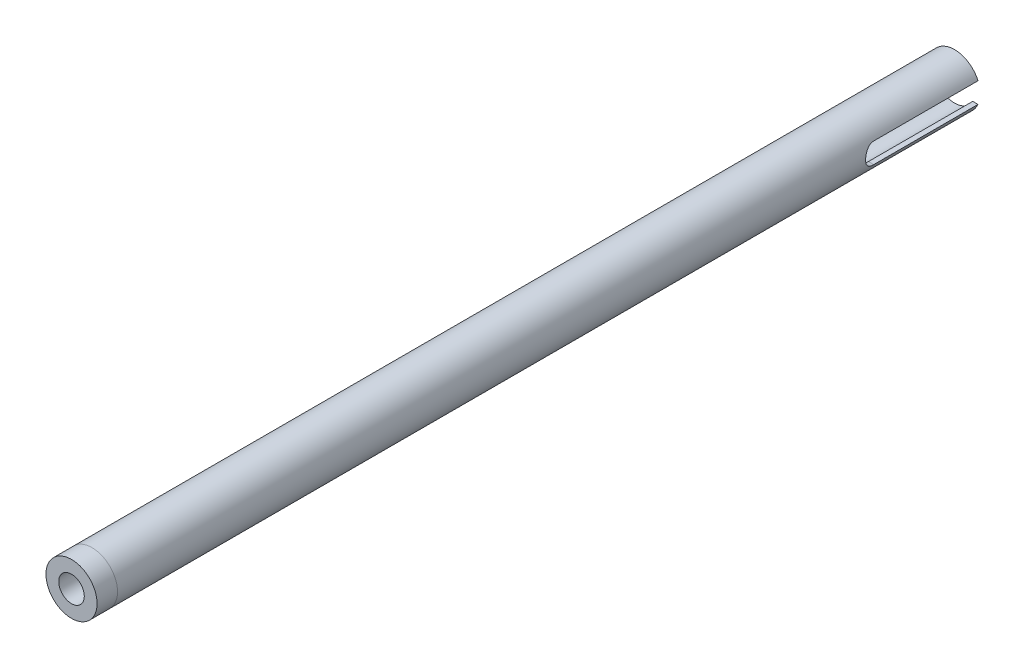
SolidWorks part; units mm, degrees
material "AISI 4130 Steel, annealed at 865C"
ref_plane "Front Plane" through (0, 0, 0) normal (0, 0, 1) x (1, 0, 0)
ref_plane "Top Plane" through (0, 0, 0) normal (0, 1, 0) x (1, 0, 0)
ref_plane "Right Plane" through (0, 0, 0) normal (1, 0, 0) x (0, 0, -1)
sketch "Axis" plane through (0, 0, 0) normal (0, 1, 0) x (1, 0, 0)
  line L0 (0, 0) -> (0, 274.208) construction
  line L1 (0, 0) -> (0, -28.575) construction
  line L2 (0, 274.208) -> (-7.9375, 274.208) construction
  line L4 (0, 295.0656) -> (-10.3187, 267.9508) construction
  dimension "D1" = 28.575
  dimension "D2" = 7.9375
sketch "Sketch1" plane through (0, 0, 0) normal (0, 0, 1) x (1, 0, 0)
  line L0 (-7.9375, 0) -> (7.9375, 0) construction
  line L1 (-7.2748, 3.175) -> (7.2748, 3.175)
  line L2 (-7.2748, -3.175) -> (7.2748, -3.175)
  circle A0 centre (0, 0) radius 7.9375
  circle A1 centre (0, 0) radius 6.4643
  circle A2 centre (0, 0) radius 3.9688
  dimension "D1" = 15.875
  dimension "D3" = 7.9375
  dimension "D2" = 1.4732
  dimension "D4" = 6.35
extrude "Threaded insert 1-1" add sketch "Sketch1" against normal blind 6.35 contours A2 L1 A1 | A1 L1 A0 | A2 L0 A1 L1 | A1 L0 A0 L1 | L0 A1 L2 A0 | L0 A2 L2 A1 | A2 L2 A1 | A1 L2 A0 | L0 A1 L2 A2 | L0 A0 L2 A1 | A0 L0 A1 L1 | A1 L0 A2 L1 region at (4.8156, 1.6537, 0) region at (4.8156, -1.6537, 0) region at (6.9501, 1.6161, 0) region at (6.9501, -1.6161, 0) region at (-4.8156, -1.6537, 0) region at (-4.8156, 1.6537, 0) region at (0, 4.6361, 0) region at (0, -4.6361, 0) region at (0, 6.6174, 0) region at (6.4528, -3.3281, 0) region at (-6.9501, -1.6161, 0) region at (-6.9501, 1.6161, 0)
extrude "Threaded insert 1-2" add sketch "Sketch1<3>" against normal blind 9.525 from surface contours A2 L1 A1 | A2 L0 A1 L1 | L0 A2 L2 A1 | A2 L2 A1 | L0 A1 L2 A2 | A1 L0 A2 L1 region at (4.8156, 1.6537, 0) region at (4.8156, -1.6537, 0) region at (-4.8156, -1.6537, 0) region at (-4.8156, 1.6537, 0) region at (0, 4.6361, 0) region at (0, -4.6361, 0) starting at face at (7.9375, 0, -6.35)
sketch "Sketch1<3>" plane through (0, 0, 0) normal (0, 0, 1) x (1, 0, 0) same geometry as "Sketch1"
extrude "A-arm tube" add sketch "Sketch1<4>" against normal up to vertex (274.208 mm away) from surface separate body contours A1 L1 A0 | A1 L0 A0 L1 | L0 A1 L2 A0 | A1 L2 A0 | L0 A0 L2 A1 | A0 L0 A1 L1 region at (6.9501, 1.6161, 0) region at (6.9501, -1.6161, 0) region at (0, 6.6174, 0) region at (6.4528, -3.3281, 0) region at (-6.9501, -1.6161, 0) region at (-6.9501, 1.6161, 0) up to point (0, 0, -274.208) starting at face at (6.4643, 0, -6.35)
sketch "Sketch1<4>" plane through (0, 0, 0) normal (0, 0, 1) x (1, 0, 0) same geometry as "Sketch1"
extrude "Apex slot" cut sketch "Sketch1<5>" along normal blind 35.56 from surface contours A0 L0 A1 L1 | L0 A0 L2 A1 | A1 L0 A0 L1 | L0 A1 L2 A0 region at (6.9501, 1.6161, 0) region at (6.9501, -1.6161, 0) region at (-6.9501, -1.6161, 0) region at (-6.9501, 1.6161, 0) starting at face at (6.4643, 0, -274.208)
sketch "Sketch1<5>" plane through (0, 0, 0) normal (0, 0, 1) x (1, 0, 0) same geometry as "Sketch1"
fillet "Fillet1" radius 3.175 4 edges at (-6.4528, 3.175, -238.648) (-6.4528, -3.175, -238.648) (6.4528, -3.175, -238.648) (6.4528, 3.175, -238.648)
equation "\"tube diameter\"= 5 / 8"
equation "\"tube thickness\"= .058"
equation "\"apex thickness\"= .25"
equation "\"tube slot\"= 1.4"
equation "\"D1@Sketch1\"=\"tube diameter\""
equation "\"D2@Sketch1\"=\"tube thickness\""
equation "\"threaded insert hole\"= .3125"
equation "\"D3@Sketch1\"=\"threaded insert hole\""
equation "\"D4@Sketch1\"=\"apex thickness\""
equation "\"D1@Apex slot\" = \"tube slot\""
equation "\"D1@Fillet1\"=\"apex thickness\"/2"
